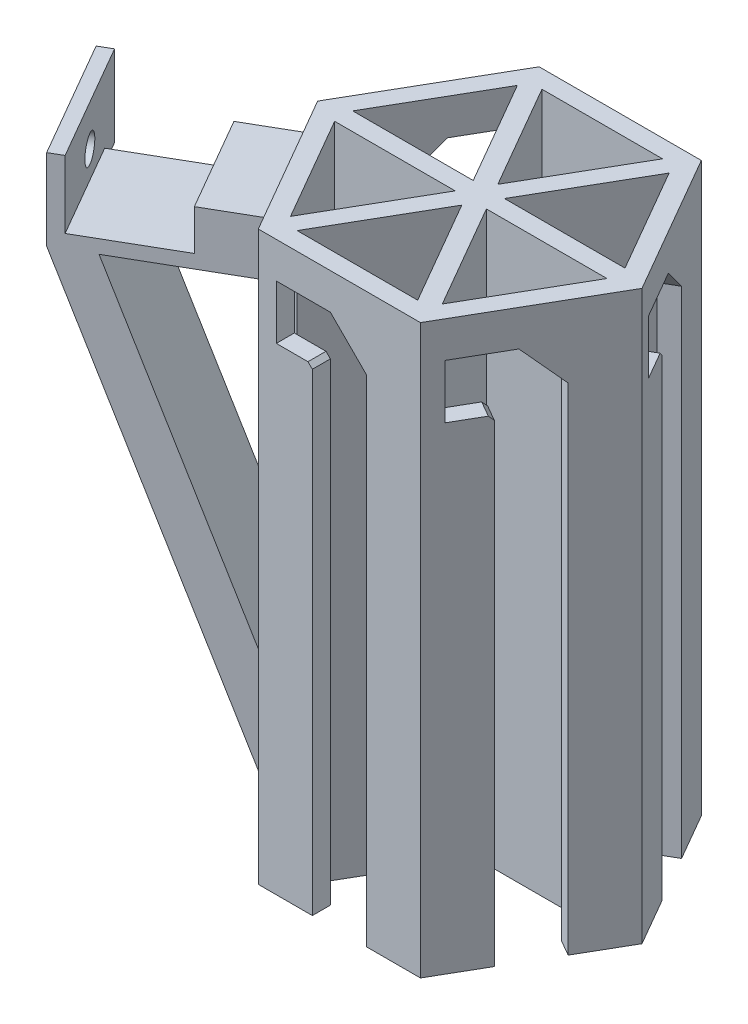
SolidWorks part; units mm, degrees
ref_plane "Alzado" through (0, 0, 0) normal (0, 0, 1) x (1, 0, 0)
ref_plane "Planta" through (0, 0, 0) normal (0, 1, 0) x (1, 0, 0)
ref_plane "Vista lateral" through (0, 0, 0) normal (1, 0, 0) x (0, 0, -1)
sketch "Croquis1" plane through (0, 0, 0) normal (0, 1, 0) x (1, 0, 0)
  line L0 (-30, 51.9615) -> (0, 0) construction
  line L1 (-60, 0) -> (-30, -51.9615) construction
  line L2 (-30, -51.9615) -> (30, -51.9615) construction
  line L3 (30, -51.9615) -> (60, 0) construction
  line L4 (60, 0) -> (30, 51.9615) construction
  line L5 (30, 51.9615) -> (-30, 51.9615) construction
  line L6 (-30, 51.9615) -> (-60, 0) construction
  line L7 (-12, 51.9615) -> (18, 0) construction
  line L8 (18, 0) -> (0, 0) construction
  line L9 (-39, 36.3731) -> (-9, -15.5885) construction
  line L10 (0, 0) -> (-9, -15.5885) construction
  line L11 (39, 36.3731) -> (9, -15.5885) construction
  line L12 (12, 51.9615) -> (-18, 0) construction
  line L13 (51, -15.5885) -> (-9, -15.5885) construction
  line L14 (51, 15.5885) -> (-9, 15.5885) construction
  line L15 (12, -51.9615) -> (-18, 0) construction
  line L16 (39, -36.3731) -> (9, 15.5885) construction
  line L17 (-39, -36.3731) -> (-9, 15.5885) construction
  line L18 (-12, -51.9615) -> (18, 0) construction
  line L19 (-51, 15.5885) -> (9, 15.5885) construction
  line L20 (-51, -15.5885) -> (9, -15.5885) construction
  line L21 (-12, 51.9615) -> (-30, 51.9615)
  line L22 (-30, 51.9615) -> (-39, 36.3731)
  line L23 (-39, 36.3731) -> (-27, 15.5885)
  line L24 (-12, 51.9615) -> (0, 31.1769)
  line L25 (39, 36.3731) -> (30, 51.9615)
  line L26 (30, 51.9615) -> (12, 51.9615)
  line L27 (12, 51.9615) -> (0, 31.1769)
  line L28 (39, 36.3731) -> (27, 15.5885)
  line L29 (51, -15.5885) -> (60, 0)
  line L30 (60, 0) -> (51, 15.5885)
  line L31 (51, 15.5885) -> (27, 15.5885)
  line L32 (51, -15.5885) -> (27, -15.5885)
  line L33 (12, -51.9615) -> (30, -51.9615)
  line L34 (30, -51.9615) -> (39, -36.3731)
  line L35 (39, -36.3731) -> (27, -15.5885)
  line L36 (12, -51.9615) -> (0, -31.1769)
  line L37 (-39, -36.3731) -> (-30, -51.9615)
  line L38 (-30, -51.9615) -> (-12, -51.9615)
  line L39 (-12, -51.9615) -> (0, -31.1769)
  line L40 (-39, -36.3731) -> (-27, -15.5885)
  line L41 (-51, 15.5885) -> (-60, 0)
  line L42 (-60, 0) -> (-51, -15.5885)
  line L43 (-51, -15.5885) -> (-27, -15.5885)
  line L44 (-51, 15.5885) -> (-27, 15.5885)
  circle A0 centre (0, 0) radius 51.9615 construction
  point P1 (-12, 51.9615)
  point P17 (39, 36.3731)
  point P22 (51, -15.5885)
  point P27 (12, -51.9615)
  point P32 (-39, -36.3731)
  point P37 (-51, 15.5885)
  point P42 (0, 0)
  point P70 (0, 0)
  dimension "D1" = 120
  dimension "D2" = 18
  dimension "D3" = 6
  dimension "D4" = 6
extrude "Saliente-Extruir1" add sketch "Croquis1" along normal blind 10
sketch "Croquis2" plane through (0, 10, 0) normal (0, 1, 0) x (1, 0, 0)
  line L0 (2.3094, 0) -> (0, 0) construction
  line L1 (-18, 31.1769) -> (-36, 0)
  line L2 (-36, 0) -> (-18, -31.1769)
  line L3 (-18, -31.1769) -> (18, -31.1769)
  line L4 (18, -31.1769) -> (36, 0)
  line L5 (36, 0) -> (18, 31.1769)
  line L6 (18, 31.1769) -> (-18, 31.1769)
  line L7 (-18, 31.1769) -> (0, 0) construction
  line L8 (-15.6906, 27.1769) -> (-31.3812, 0)
  line L9 (-31.3812, 0) -> (-15.6906, -27.1769)
  line L10 (-15.6906, -27.1769) -> (15.6906, -27.1769)
  line L11 (15.6906, -27.1769) -> (31.3812, 0)
  line L12 (31.3812, 0) -> (15.6906, 27.1769)
  line L13 (15.6906, 27.1769) -> (-15.6906, 27.1769)
  line L14 (-15.6906, 31.1769) -> (2.3094, 0) construction
  line L15 (-19.1547, 29.1769) -> (-1.1547, -2) construction
  line L16 (-1.1547, -2) -> (0, 0) construction
  line L17 (19.1547, 29.1769) -> (1.1547, -2) construction
  line L18 (15.6906, 31.1769) -> (-2.3094, 0) construction
  line L19 (34.8453, -2) -> (-1.1547, -2) construction
  line L20 (34.8453, 2) -> (-1.1547, 2) construction
  line L21 (15.6906, -31.1769) -> (-2.3094, 0) construction
  line L22 (19.1547, -29.1769) -> (1.1547, 2) construction
  line L23 (-19.1547, -29.1769) -> (-1.1547, 2) construction
  line L24 (-15.6906, -31.1769) -> (2.3094, 0) construction
  line L25 (-34.8453, 2) -> (1.1547, 2) construction
  line L26 (-34.8453, -2) -> (1.1547, -2) construction
  line L27 (-15.6906, 27.1769) -> (-16.8453, 25.1769)
  line L28 (-16.8453, 25.1769) -> (-3.4641, 2)
  line L29 (-15.6906, 27.1769) -> (-13.3812, 27.1769)
  line L30 (-13.3812, 27.1769) -> (0, 4)
  line L31 (16.8453, 25.1769) -> (3.4641, 2)
  line L32 (31.3812, 0) -> (15.6906, 27.1769)
  line L33 (15.6906, 27.1769) -> (-15.6906, 27.1769)
  line L34 (13.3812, 27.1769) -> (0, 4)
  line L35 (30.2265, -2) -> (3.4641, -2)
  line L36 (15.6906, -27.1769) -> (31.3812, 0)
  line L37 (31.3812, 0) -> (15.6906, 27.1769)
  line L38 (30.2265, 2) -> (3.4641, 2)
  line L39 (13.3812, -27.1769) -> (0, -4)
  line L40 (-15.6906, -27.1769) -> (15.6906, -27.1769)
  line L41 (15.6906, -27.1769) -> (31.3812, 0)
  line L42 (16.8453, -25.1769) -> (3.4641, -2)
  line L43 (-16.8453, -25.1769) -> (-3.4641, -2)
  line L44 (-31.3812, 0) -> (-15.6906, -27.1769)
  line L45 (-15.6906, -27.1769) -> (15.6906, -27.1769)
  line L46 (-13.3812, -27.1769) -> (0, -4)
  line L47 (-30.2265, 2) -> (-3.4641, 2)
  line L48 (-15.6906, 27.1769) -> (-31.3812, 0)
  line L49 (-31.3812, 0) -> (-15.6906, -27.1769)
  line L50 (-30.2265, -2) -> (-3.4641, -2)
  circle A0 centre (0, 0) radius 31.1769 construction
  circle A1 centre (0, 0) radius 27.1769 construction
  point P43 (0, 0)
  point P83 (0, 0)
  dimension "D1" = 4
  dimension "D2" = 2
  dimension "D3" = 6
  dimension "D4" = 6
extrude "Saliente-Extruir2" add sketch "Croquis2" along normal blind 170 contours L5 L6 L1 L2 L3 L4 L13 L12 L37 L11 L41 L10 L45 L9 L49 L8 L33 | L9 L50 L43 L10 L46 L39 L11 L42 L35 L12 L38 L31 L13 L34 L30 L8 L28 L47 region at (0, 10, -30.2244) region at (0, 10, 0)
sketch "Croquis3" plane through (0, 0, 31.1769) normal (0, 0, 1) x (1, 0, 0)
  line L0 (-14, 172) -> (-2, 172)
  line L1 (-2, 172) -> (6, 164)
  line L2 (6, 164) -> (6, 44)
  line L3 (-18, 180) -> (18, 180) construction
  line L4 (-18, 180) -> (-18, 10) construction
  line L5 (18, 180) -> (18, 10) construction
  line L6 (-14, 160) -> (-6.9706, 160)
  line L7 (-6.9706, 160) -> (-6, 159.0294)
  line L8 (-6, 159.0294) -> (-6, 44)
  line L9 (-14, 172) -> (-14, 160)
  line L10 (-6, 44) -> (6, 44)
  dimension "D1" = 8
  dimension "D2" = 4
  dimension "D3" = 12
  dimension "D4" = 135
  dimension "D5" = 120
  dimension "D6" = 12
  dimension "D7" = 12
extrude "Cortar-Extruir1" cut sketch "Croquis3" against normal blind 4
pattern_circular "MatrizC1" count 5 every 60 about axis through (0, 180, 0) along (0, 1, 0) of "Cortar-Extruir1"
sketch "Croquis4" plane through (-27, 0, 15.5885) normal (-0.866, 0, 0.5) x (0.5, 0, 0.866)
  line L2 (-18, 180) -> (18, 10) construction
  line L3 (0, 95) -> (0, 172) construction
  line L4 (-18, 180) -> (18, 180) construction
  line L6 (12, 166) -> (-12, 166)
  line L7 (12, 166) -> (12, 178)
  line L8 (12, 178) -> (-12, 178)
  line L9 (-12, 166) -> (-12, 178)
  line L10 (12, 166) -> (-12, 178) construction
  line L11 (12, 178) -> (-12, 166) construction
  line L12 (0, 178) -> (0, 180) construction
  point P6 (0, 172)
  point P7 (0, 172)
  dimension "D1" = 8
  dimension "D2" = 12
  dimension "D3" = 24
extrude "Saliente-Extruir3" add sketch "Croquis4" along normal blind 36 contours L9 L6 L7 L8 region at (-27, 172, 15.5885)
sketch "Croquis5" plane through (-58.1769, 0, 33.5885) normal (-0.866, 0, 0.5) x (0.5, 0, 0.866)
  line L0 (-12, 169) -> (12, 169)
  line L1 (-12, 166) -> (-12, 178) construction
  line L2 (12, 166) -> (12, 178) construction
  line L3 (12, 166) -> (-12, 166) construction
  line L4 (-12, 169) -> (-12, 178)
  line L5 (-12, 166) -> (-12, 178) construction
  line L6 (-12, 178) -> (12, 178)
  line L7 (12, 178) -> (12, 169)
  dimension "D1" = 3
extrude "Cortar-Extruir2" cut sketch "Croquis5" against normal blind 24
chamfer "Chaflán1" distance 36 angle 70 1 edges at (-27, 166, 15.5885) first distance on face at (-42.5885, 166, 24.5885)
sketch "Croquis6" plane through (-6, 0, -10.3923) normal (-0.5, 0, -0.866) x (-0.866, 0, 0.5)
  line L0 (67.1769, 166) -> (31.1769, 67.0908) construction
  line L1 (31.1769, 67.0908) -> (31.1769, 166) construction
  line L2 (31.1769, 67.0908) -> (31.1769, 178) construction
  line L3 (31.1769, 166) -> (58.6635, 166) construction
  line L4 (58.6635, 166) -> (31.1769, 90.4812)
  line L5 (59.6594, 168.7362) -> (23.6594, 69.827) construction
  line L6 (58.6635, 166) -> (67.1769, 166) construction
  line L7 (31.1769, 90.4812) -> (31.1769, 166)
  line L8 (31.1769, 166) -> (58.6635, 166)
  dimension "D1" = 8
extrude "Cortar-Extruir3" cut sketch "Croquis6" against normal blind 24
sketch "Croquis7" plane through (-58.1769, 0, 33.5885) normal (-0.866, 0, 0.5) x (0.5, 0, 0.866)
  line L1 (12, 166) -> (-18, 166)
  line L2 (12, 166) -> (12, 184)
  line L3 (12, 184) -> (-18, 184)
  line L4 (-18, 166) -> (-18, 184)
  circle A0 centre (-3, 175) radius 3
  dimension "D5" = 6
  dimension "D1" = 30
  dimension "D2" = 18
  dimension "D3" = 9
  dimension "D4" = 15
extrude "Saliente-Extruir4" add sketch "Croquis7" against normal blind 3
ref_plane "Plano1" through (0, 54, 0) normal (0, 1, 0) x (1, 0, 0)
sketch "Croquis8" plane through (0, 54, 0) normal (0, 1, 0) x (1, 0, 0)
  line L1 (125, -125) -> (-125, -125)
  line L2 (125, -125) -> (125, 125)
  line L3 (125, 125) -> (-125, 125)
  line L4 (-125, -125) -> (-125, 125)
  line L5 (125, -125) -> (-125, 125) construction
  line L6 (125, 125) -> (-125, -125) construction
  point P0 (0, 0)
  dimension "D1" = 250
extrude "Cortar-Extruir4" cut sketch "Croquis8" against normal blind 84
sketch "Croquis9" plane through (0, 54, 0) normal (0, -1, 0) x (1, 0, 0)
  circle A0 centre (0, 0) radius 2.5
  dimension "D1" = 5
extrude "Cortar-Extruir5" cut sketch "Croquis9" against normal blind 2
sketch "Croquis10" plane through (0, 56, 0) normal (0, -1, 0) x (1, 0, 0)
  line L0 (-1.5289, 0.95) -> (1.5289, 0.95)
  line L1 (-1.5289, -0.95) -> (1.5289, -0.95)
  circle A0 centre (0, 0) radius 1.8
  circle A1 centre (0, 0) radius 0.95 construction
  dimension "D1" = 3.6
  dimension "D2" = 1.9
extrude "Cortar-Extruir6" cut sketch "Croquis10" against normal blind 7.9 contours L1 A0 L0 region at (0, 56, 0)
